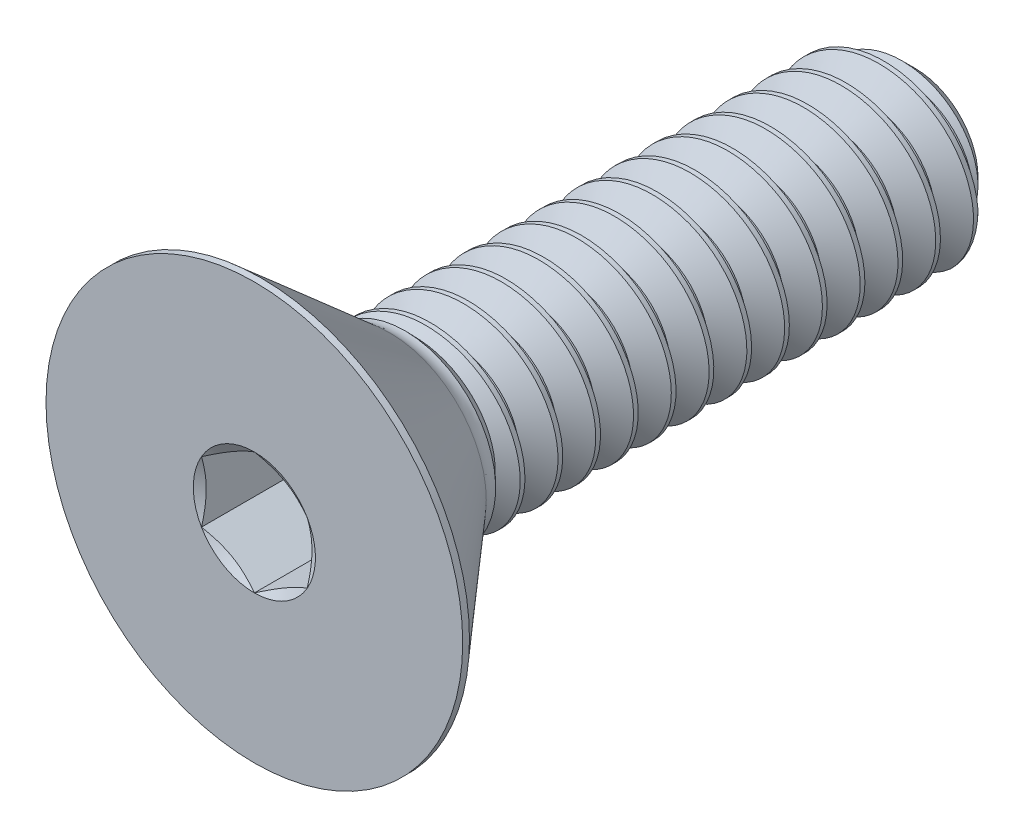
SolidWorks part; units mm, degrees
ref_plane "Front" through (0, 0, 0) normal (0, 0, 1) x (1, 0, 0)
ref_plane "Top" through (0, 0, 0) normal (0, 1, 0) x (1, 0, 0)
ref_plane "Right" through (0, 0, 0) normal (1, 0, 0) x (0, 0, -1)
sketch "Sketch1" plane through (0, 0, 0) normal (1, 0, 0) x (0, 0, -1)
  line L0 (0, 2.5019) -> (0.0813, 2.5019) construction
  line L1 (0.0813, 2.5019) -> (1.6256, 1.1594) construction
  line L2 (0, 1.0922) -> (7.9375, 1.0922)
  line L3 (7.9375, 1.0922) -> (7.9375, 0)
  line L4 (7.9375, 0) -> (0, 0)
  line L5 (0, 0) -> (0, 2.5019) construction
  line L6 (0, 2.5019) -> (0, -2.5019) construction
  line L7 (7.9375, 1.0922) -> (7.9375, -1.0922) construction
  line L8 (0, -2.5019) -> (0.0813, -2.5019) construction
  line L9 (0.0813, -2.5019) -> (1.6256, -1.1594) construction
  line L11 (0, 1.0922) -> (0, 0)
  line L12 (1.8054, 1.0922) -> (1.8054, 0) construction
  line L13 (-17.4625, 0) -> (-17.4625, 1.0922) construction
  arc A1 (1.6256, 1.1594) -> (1.8054, 1.0922) centre (1.8054, 1.3663) ccw construction
  dimension "D1" = 0.0813
  dimension "Min Thread" = 25.4
revolve "Revolve1" add sketch "Sketch1" angle 360 mid plane about L4
sketch "Sketch3" plane through (0, 0, -7.9375) normal (0, 0, -1) x (-1, 0, 0)
  circle A0 centre (0, 0) radius 1.0922
curve "Helix/Spiral1" pitch 0.4536 height 7.9375 radius 1.0922 centre (0, 0, -7.9375) axis (0, 0, 1) start towards (0, 1, 0)
sketch "Sketch2" plane through (0, 0, 0) normal (1, 0, 0) x (0, 0, -1)
  line L0 (7.9375, 1.0922) -> (8.3344, 1.0922)
  line L1 (8.3344, 1.0922) -> (8.1643, 0.7976)
  line L2 (8.1643, 0.7976) -> (8.1076, 0.7976)
  line L3 (8.1076, 0.7976) -> (7.9375, 1.0922)
  line L4 (8.0225, 0.9449) -> (8.2493, 0.9449) construction
  dimension "D1" = 60
  dimension "D2" = 0.0567
  dimension "D3" = 0.2268
ref_plane "Plane2" through (0, 0, 17.4625) normal (0, 0, 1) x (1, 0, 0)
chamfer "Chamfer1" distance 0.3402 angle 45 1 edges at (-1.0922, 0, -7.9375)
sweep "Cut-Sweep1" cut profiles "Sketch2" path "Helix/Spiral1" align with end faces yes
sketch "Sketch7" plane through (0, 0, 0) normal (1, 0, 0) x (0, 0, -1)
  line L0 (0, 2.5019) -> (0.0813, 2.5019) construction
  line L1 (0.0813, 2.5019) -> (1.6256, 1.1594) construction
  line L2 (0, 2.5019) -> (0.0813, 2.5019)
  line L3 (0.0813, 2.5019) -> (1.6256, 1.1594)
  line L4 (1.8054, 1.0922) -> (1.8054, 0) construction
  line L5 (1.8054, 1.0922) -> (1.8054, 0)
  line L7 (0, 0) -> (0, 2.5019) construction
  line L8 (0, 0) -> (0, 2.5019)
  line L9 (0, 0) -> (1.8054, 0)
  line L10 (5.7417, 0) -> (-5.7417, 0) construction
  arc A0 (1.6256, 1.1594) -> (1.8054, 1.0922) centre (1.8054, 1.3663) ccw construction
  arc A1 (1.6256, 1.1594) -> (1.8054, 1.0922) centre (1.8054, 1.3663) ccw
revolve "Revolve2" add sketch "Sketch7" angle 360 mid plane about L9
ref_plane "Plane1" through (0, 0, -1.8054) normal (0, 0, 1) x (1, 0, 0)
sketch "Sketch8" plane through (0, 0, -1.8054) normal (0, 0, 1) x (1, 0, 0)
  circle A0 centre (0, 0) radius 1.0922
extrude "Boss-Extrude1" add sketch "Sketch8" against normal through all draft 46
sketch "Sketch5" plane through (0, 0, 0) normal (0, 0, 1) x (1, 0, 0)
  line L0 (0, 0) -> (-0.7332, 0) construction
  line L1 (0, 0) -> (-2.7496, 1.5875) construction
  line L2 (0, 0) -> (-2.7496, -1.5875) construction
  line L6 (0, 0.7332) -> (0, 0.6047) construction
  line L7 (0, 0.6047) -> (0, 0.4763) construction
  line L9 (0, 0.7332) -> (-0.635, 0.3666)
  line L10 (-0.635, 0.3666) -> (-0.635, -0.3666)
  line L11 (-0.635, -0.3666) -> (0, -0.7332)
  line L12 (0, -0.7332) -> (0.635, -0.3666)
  line L13 (0.635, -0.3666) -> (0.635, 0.3666)
  line L14 (0.635, 0.3666) -> (0, 0.7332)
  circle A0 centre (0, 0) radius 0.7332 construction
  circle A1 centre (0, 0) radius 0.6047 construction
  circle A2 centre (0, 0) radius 0.4763 construction
  circle A3 centre (0, 0) radius 0.635 construction
  dimension "D3" = 0.9525
  dimension "D4" = 30
  dimension "D5" = 30
  dimension "Hex" = 1.27
extrude "Cut-Extrude2" cut sketch "Sketch5" against normal blind 1.1379
sketch "Sketch6" plane through (0, 0, 0) normal (0, 0, 1) x (1, 0, 0)
  circle A0 centre (0, 0) radius 0.7332
extrude "Cut-Extrude3" cut sketch "Sketch6" against normal blind 1.1379 draft 60
sketch "Sketch9" [suppressed] plane through (0, 0, -3.6076) normal (0, 0, 1) x (1, 0, 0)
  circle A1 centre (0, 0) radius 2.413
  circle A2 centre (0, 0) radius 2.413
  point P0 (0, 2.413)
  dimension "D1" = 0
extrude "Boss-Extrude2" [suppressed] add sketch "Sketch9" against normal up to surface (15.4424 mm away) up to plane "Plane2"
sketch "Sketch10" plane through (0, 0, 0) normal (1, 0, 0) x (0, 0, -1)
  line L0 (7.9375, 1.0922) -> (7.9375, -1.0922) construction
  point P0 (7.2571, -1.0922)
  dimension "D1" = 0.6804
equation "\"D3@Helix/Spiral1\" = \"Lg@Sketch1\""
equation "\"D2@Sketch2\" = \"D4@Helix/Spiral1\" * .125"
equation "\"D3@Sketch2\" = \"D4@Helix/Spiral1\" * .5"
equation "\"D1@Chamfer1\" = \"D4@Helix/Spiral1\" * .75"
equation "\"D1@Cut-Extrude2\" = \"Head Ht@Sketch1\" * .7"
equation "\"D1@Sketch1\" = \"Head Ht@Sketch1\" * .05"
equation "\"D1@Sketch10\" = \"D4@Helix/Spiral1\" * 1.5"
equation "\"D1@Cut-Extrude3\" = \"D1@Cut-Extrude2\""
equation "\"D3@Sketch5\" = \"Hex@Sketch5\" * .75"
